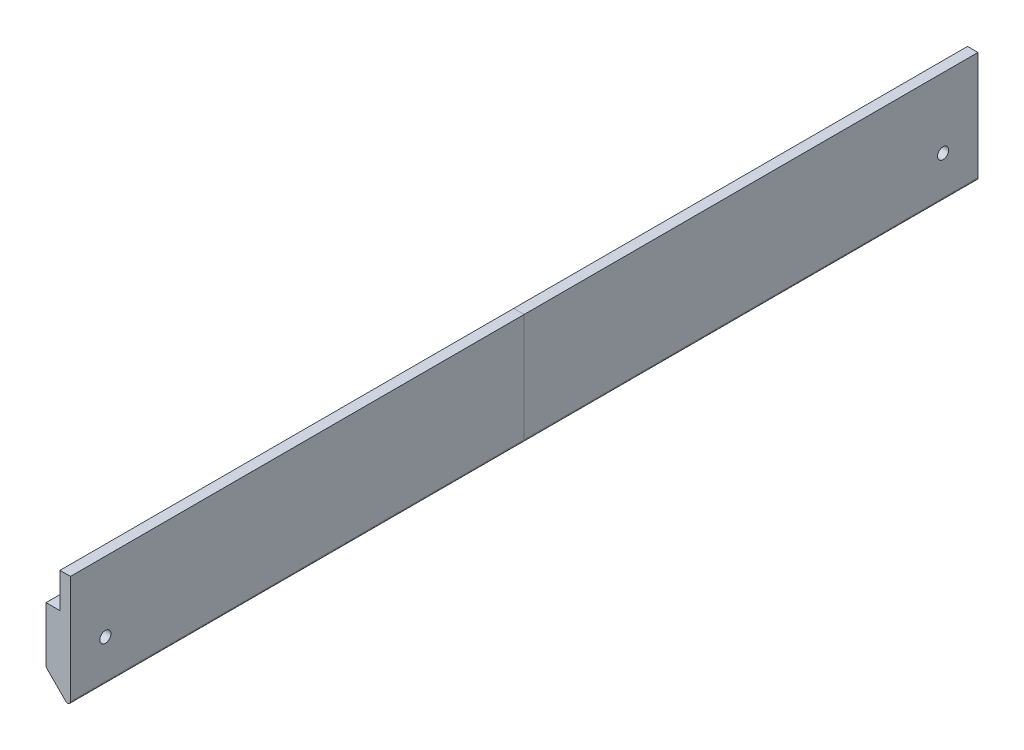
SolidWorks part; units mm, degrees
ref_plane "Front Plane" through (0, 0, 0) normal (0, 0, 1) x (1, 0, 0)
ref_plane "Top Plane" through (0, 0, 0) normal (0, 1, 0) x (1, 0, 0)
ref_plane "Right Plane" through (0, 0, 0) normal (1, 0, 0) x (0, 0, -1)
ref_plane "Plane1" through (0, 0, 280) normal (0, 0, 1) x (1, 0, 0)
sketch "Sketch1" plane through (0, 0, 280) normal (0, 0, 1) x (1, 0, 0)
  line L0 (-7, 4) -> (4, -7)
  line L1 (4, -7) -> (7, -7)
  line L2 (7, -7) -> (7, -3)
  line L3 (7, -3) -> (20, -3)
  line L4 (20, -3) -> (20, 0)
  line L5 (20, 0) -> (0, 0)
  line L6 (0, 0) -> (0, 20)
  line L7 (0, 20) -> (-3, 20)
  line L8 (-3, 20) -> (-3, 7)
  line L9 (-3, 7) -> (-7, 7)
  line L10 (-7, 7) -> (-7, 4)
extrude "Boss-Extrude1" add sketch "Sketch1" against normal blind 260
fillet "Fillet1" radius 1.5 2 edges at (-7, 4, 150) (4, -7, 150)
sketch "Sketch2" plane through (0, 0, 0) normal (0, 1, 0) x (1, 0, 0)
  line L4 (0, -280) -> (20, -280)
  line L5 (20, -280) -> (20, -20)
  line L6 (20, -20) -> (0, -20)
  line L7 (0, -20) -> (0, -280)
  line L8 (0, -280) -> (20, -280)
  line L9 (20, -280) -> (20, -20)
  line L10 (20, -20) -> (0, -20)
  line L11 (0, -20) -> (0, -280)
  dimension "D1" = 0
extrude "Cut-Extrude1" cut sketch "Sketch2" against normal blind 10
fillet "Fillet2" radius 0.8 1 edges at (0, -3, 150)
sketch "Sketch3" plane through (-3, 0, 0) normal (-1, 0, 0) x (0, 0, 1)
  line L4 (280, 7) -> (280, 20)
  line L5 (280, 20) -> (20, 20)
  line L6 (20, 20) -> (20, 7)
  line L7 (20, 7) -> (280, 7)
  line L8 (280, 7) -> (280, 20)
  line L9 (280, 20) -> (20, 20)
  line L10 (20, 20) -> (20, 7)
  line L11 (20, 7) -> (280, 7)
  dimension "D1" = 0
sketch "Sketch4" plane through (0, 20, 0) normal (0, 1, 0) x (1, 0, 0)
  line L4 (-3, -280) -> (0, -280)
  line L5 (0, -280) -> (0, -20)
  line L6 (0, -20) -> (-3, -20)
  line L7 (-3, -20) -> (-3, -280)
  line L8 (-3, -280) -> (0, -280)
  line L9 (0, -280) -> (0, -20)
  line L10 (0, -20) -> (-3, -20)
  line L11 (-3, -20) -> (-3, -280)
  dimension "D1" = 0
extrude "Boss-Extrude2" add sketch "Sketch4" along normal blind 10
extrude "Boss-Extrude3" add sketch "Sketch3" along normal blind 4
sketch "Sketch5" plane through (-7, 0, 0) normal (-1, 0, 0) x (0, 0, 1)
  line L0 (30, 10) -> (270, 10) construction
  line L1 (20, 20) -> (20, 4.6213) construction
  line L2 (280, 20) -> (20, 20) construction
  line L3 (280, 20) -> (280, 4.6213) construction
  point P0 (30, 10)
  point P1 (270, 10)
  dimension "D1" = 10
  dimension "D2" = 10
  dimension "D3" = 10
hole_wizard "CSK for M3 SFHCS1" positions "Sketch5" profile "Sketch6" countersink size "M3" standard "ANSI Metric" end condition through all
sketch "Sketch6" plane through (-7, 10, 30) normal (0, 1, 0) x (0, 0, 1)
  line L0 (0, 0) -> (0, 7)
  line L1 (0, 7) -> (1.6, 7)
  line L2 (1.6, 7) -> (1.6, 1.76)
  line L3 (1.6, 1.76) -> (3.36, 0)
  line L5 (3.36, 0) -> (0, 0)
  line L6 (-1.6, 1.76) -> (-3.36, 0) construction
  line L11 (0, -6.35) -> (0, 107.95) construction
  dimension "Thru Hole Dia." = 3.2
  dimension "Thru Hole Depth" = 7
  dimension "Near C'Sink Dia." = 6.72
  dimension "Near C'Sink Angle" = 90
sketch3d "3DSketch1" plane through (0, 0, 0) normal (0, 0, 1) x (1, 0, 0)
  dimension "D1" = 130
sketch "Sketch7" plane through (0, 0, 150) normal (0, 0, 1) x (1, 0, 0)
  line L1 (-34.9326, 43.1916) -> (28.35, 43.1916)
  line L2 (-34.9326, 43.1916) -> (-34.9326, -9.3722)
  line L3 (-34.9326, -9.3722) -> (28.35, -9.3722)
  line L4 (28.35, 43.1916) -> (28.35, -9.3722)
  point P4 (3.8203, 14.4657)
  point P5 (8.3552, 9.7981)
  point P6 (12.4778, 4.2325)
  point P7 (28.35, -9.3722)
sketch "Sketch8" plane through (0, 0, 0) normal (1, 0, 0) x (0, 0, -1)
  line L0 (-150, 30) -> (-150, -1.8686)
  line L1 (-280, 30) -> (-20, 30) construction
  line L2 (-280, -1.8686) -> (-20, -1.8686) construction
split "Split1" trim tools "Sketch8" bodies to split 107 resulting bodies 109 110
